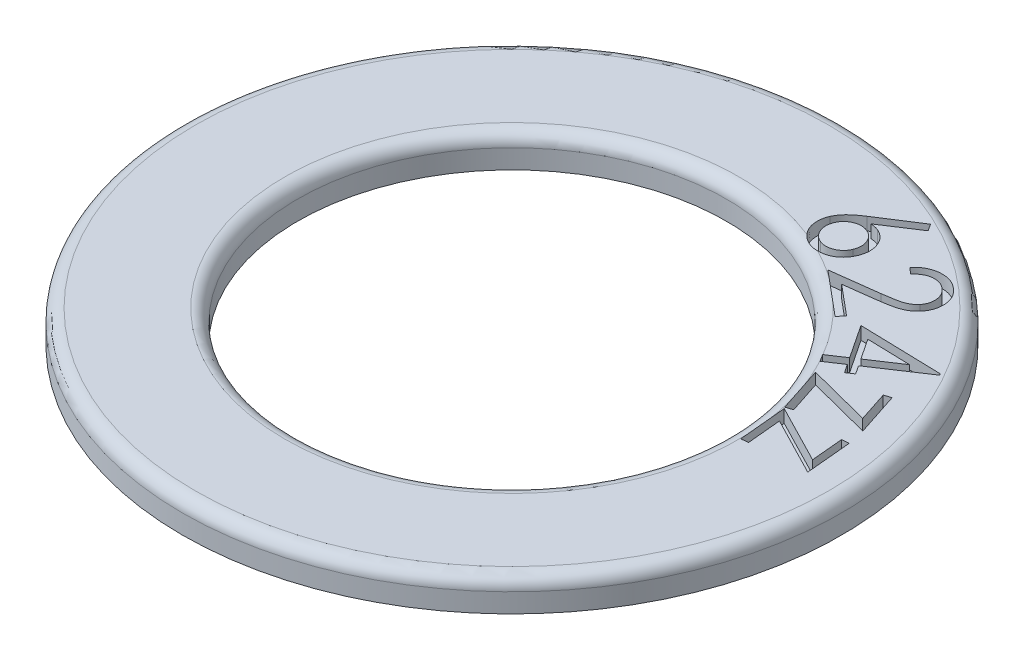
SolidWorks part; units mm, degrees
ref_plane "Alzado" through (0, 0, 0) normal (0, 0, 1) x (1, 0, 0)
ref_plane "Planta" through (0, 0, 0) normal (0, 1, 0) x (1, 0, 0)
ref_plane "Vista lateral" through (0, 0, 0) normal (1, 0, 0) x (0, 0, -1)
sketch "Croquis1" plane through (0, 0, 0) normal (0, 1, 0) x (1, 0, 0)
  circle A0 centre (0, 0) radius 3.35
  circle A1 centre (0, 0) radius 5.15
extrude "Saliente-Extruir1" add sketch "Croquis1" along normal blind 0.5
sketch "Croquis2" plane through (0, 0.5, 0) normal (0, 1, 0) x (1, 0, 0)
  line L0 (-3.35, 0) -> (-3.5724, 0) construction
  circle A0 centre (0, 0) radius 3.35 construction
  circle A2 centre (0, 0) radius 3.5724 construction
  text T0 "624zz" font "Century Gothic" height in points 5
  point P8 (-3.9015, 0)
  point P9 (0, 0)
  point P10 (0, 0)
  point P12 (-3.5724, 0)
extrude "Cortar-Extruir1" cut sketch "Croquis2" against normal blind 0.2
fillet "Redondeo1" radius 0.2 2 edges at (0, 0.5, 3.35) (0, 0.5, 5.15)
